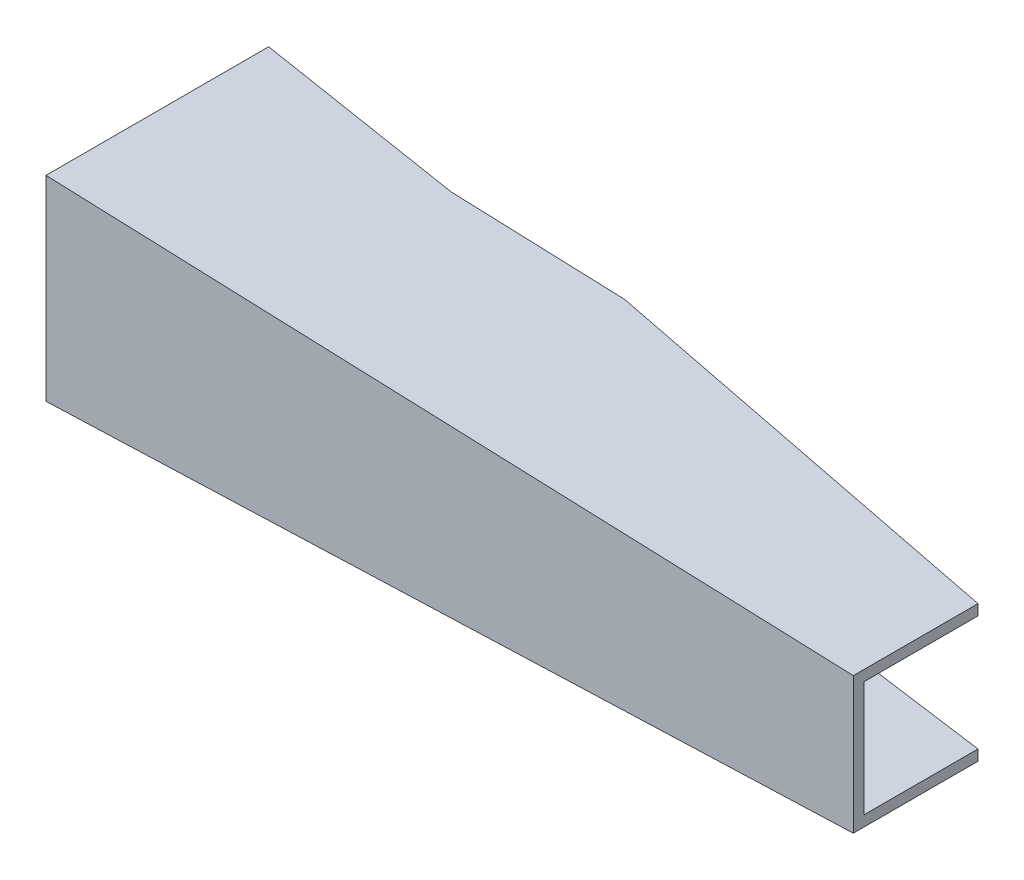
SolidWorks part; units mm, degrees
ref_plane "Front Plane" through (0, 0, 0) normal (0, 0, 1) x (1, 0, 0)
ref_plane "Top Plane" through (0, 0, 0) normal (0, 1, 0) x (1, 0, 0)
ref_plane "Right Plane" through (0, 0, 0) normal (1, 0, 0) x (0, 0, -1)
sketch "Sketch1" plane through (0, 0, 0) normal (0, 0, 1) x (1, 0, 0)
  line L0 (0, 39.555) -> (0, -39.555)
  line L1 (0, -39.555) -> (326.3, -27.585)
  line L2 (326.3, -27.585) -> (326.3, 27.585)
  line L3 (326.3, 27.585) -> (0, 39.555)
  point P4 (0, 0)
  point P6 (326.3, 0)
  dimension "D1" = 326.3
  dimension "D2" = 79.11
  dimension "D3" = 55.17
extrude "Boss-Extrude1" add sketch "Sketch1" along normal blind 105 contours L3 L0 L1 L2
sketch "Sketch3" plane through (0, 0, 0) normal (0, 1, 0) x (1, 0, 0)
  line L0 (0, -15) -> (84.7, -25.82)
  line L1 (84.7, -25.82) -> (154.7, -25.82)
  line L2 (154.7, -25.82) -> (326.3, -54.6)
  line L3 (326.3, -105) -> (326.3, 0) construction
  line L4 (326.3, -105) -> (0, -105) construction
  line L5 (0, -43.5105) -> (0, 43.5105) construction
  line L6 (0, -15) -> (0, 41.1139)
  line L7 (0, 41.1139) -> (326.3, 36.079)
  line L8 (326.3, 36.079) -> (326.3, -54.6)
  line L9 (0, -105) -> (0, 0) construction
  dimension "D1" = 79.18
  dimension "D2" = 84.7
  dimension "D3" = 70
  dimension "D4" = 50.4
  dimension "D5" = 90
extrude "Cut-Extrude1" cut sketch "Sketch3" against normal blind 105.1 and the other way blind 105.1
sketch "Sketch4" plane through (326.3, 0, 0) normal (1, 0, 0) x (0, 0, -1)
  line L0 (-105, -27.585) -> (-105, 27.585) construction
  line L1 (-100.7, 23.285) -> (-22.5545, 23.285)
  line L2 (-100.7, 23.285) -> (-100.7, -23.285)
  line L3 (-100.7, -23.285) -> (-22.5545, -23.285)
  line L4 (-22.5545, 23.285) -> (-22.5545, -23.285)
  line L5 (-105, 27.585) -> (-54.6, 27.585) construction
  line L6 (-105, -27.585) -> (-54.6, -27.585) construction
  dimension "D1" = 4.3
  dimension "D2" = 4.3
  dimension "D3" = 4.3
sketch "Sketch5" plane through (0, 0, 0) normal (-1, 0, 0) x (0, 0, 1)
  line L0 (105, 39.555) -> (15, 39.555) construction
  line L1 (-10.9565, 35.255) -> (100.7, 35.255)
  line L2 (-10.9565, 35.255) -> (-10.9565, -35.255)
  line L3 (-10.9565, -35.255) -> (100.7, -35.255)
  line L4 (100.7, 35.255) -> (100.7, -35.255)
  line L5 (105, 39.555) -> (105, -39.555) construction
  line L6 (105, -39.555) -> (15, -39.555) construction
  dimension "D1" = 4.3
  dimension "D2" = 4.3
  dimension "D3" = 4.3
loft "Cut-Loft1" cut profiles "Sketch4", "Sketch5"
equation "\"D2@Sketch4\"=\"D1@Sketch4\""
equation "\"D3@Sketch4\"=\"D1@Sketch4\""
equation "\"D2@Sketch5\"=\"D1@Sketch5\""
equation "\"D3@Sketch5\"=\"D1@Sketch5\""
